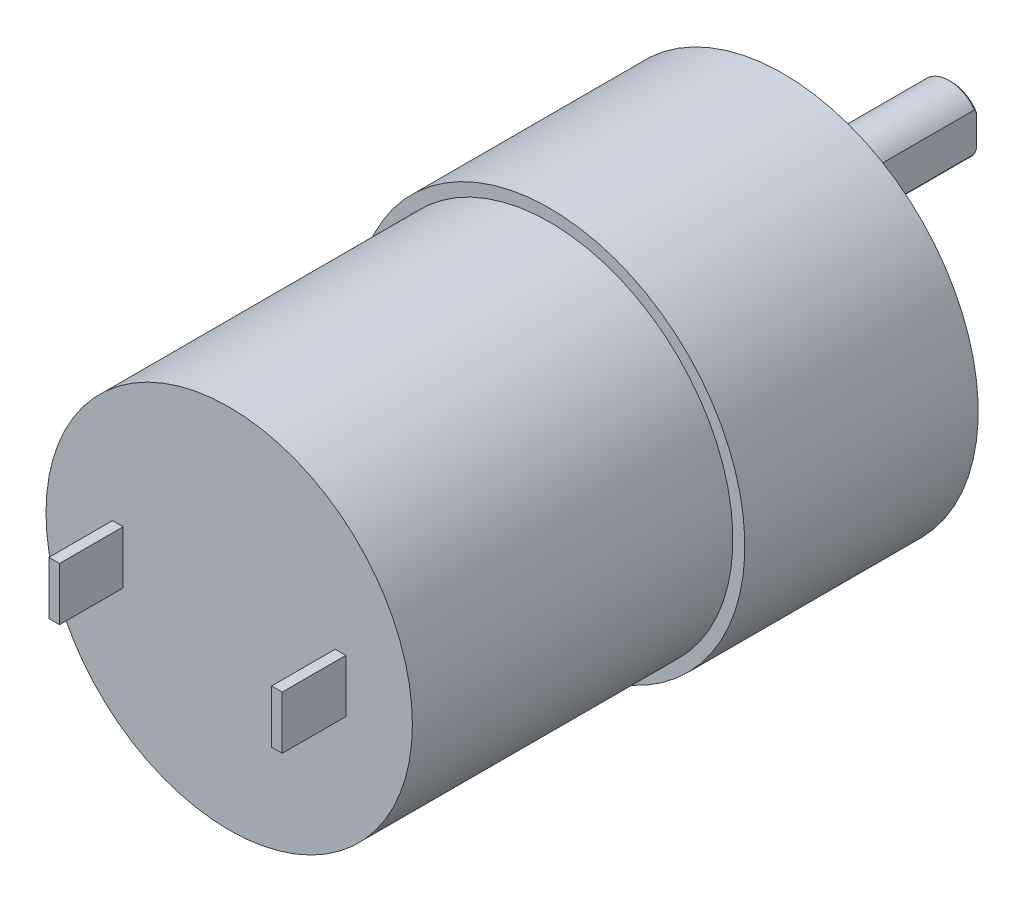
SolidWorks part; units mm, degrees
material "Plain Carbon Steel"
ref_plane "Front Plane" through (0, 0, 0) normal (0, 0, 1) x (1, 0, 0)
ref_plane "Top Plane" through (0, 0, 0) normal (0, 1, 0) x (1, 0, 0)
ref_plane "Right Plane" through (0, 0, 0) normal (1, 0, 0) x (0, 0, -1)
sketch "Sketch1" plane through (0, 0, 0) normal (0, 0, 1) x (1, 0, 0)
  line L0 (0, 0) -> (-7, 0)
  line L1 (0, 0) -> (-17.272, 0)
  line L2 (0, 0) -> (0, 17.272)
  line L3 (0, 0) -> (0, -15.5)
  line L4 (-4.6, 1.8) -> (-4.6, -1.8)
  line L5 (0, 0) -> (0, -15.5) construction
  circle A0 centre (0, 0) radius 17.272
  circle A1 centre (-7, 0) radius 3
  circle A2 centre (-7, 0) radius 6
  circle A3 centre (0, -15.5) radius 1.5
  circle A4 centre (-13.4234, -7.75) radius 1.5
  circle A5 centre (-13.4234, 7.75) radius 1.5
  circle A6 centre (0, 15.5) radius 1.5
  circle A7 centre (13.4234, 7.75) radius 1.5
  circle A8 centre (13.4234, -7.75) radius 1.5
  point P28 (0, -0.9391)
  point P31 (0, 0)
  point P35 (0, 0)
  dimension "D1" = 34.544
  dimension "D2" = 7
  dimension "D4" = 6
  dimension "D3" = 12
  dimension "D8" = 6
  dimension "D6" = 15.5
  dimension "D7" = 3
  dimension "D5" = 2.4
  dimension "D9" = 15.5
extrude "Boss-Extrude1" add sketch "Sketch1" along normal blind 52.22 contours A0
extrude "Boss-Extrude2" add sketch "Sketch1<3>" against normal blind 6.5 contours A2 A1 | L4 A1 L1 | L1 A1 L4 | L1 A2 A1 | L1 A1 L4 | L4 A1 L1 region at (-7, -5.8658, 0) region at (-2.5, 0.1342, 0) region at (-4.3578, -0.685, 0) region at (-4.3578, 0.685, 0) region at (-7.1451, -1.3055, 0) region at (-7.1451, 1.3055, 0)
sketch "Sketch1<3>" plane through (0, 0, 0) normal (0, 0, 1) x (1, 0, 0) same geometry as "Sketch1"
extrude "Boss-Extrude3" add sketch "Sketch1<4>" against normal blind 22.86 contours L4 A1 L1 | L1 A1 L4 region at (-7.1451, -1.3055, 0) region at (-7.1451, 1.3055, 0)
sketch "Sketch1<4>" plane through (0, 0, 0) normal (0, 0, 1) x (1, 0, 0) same geometry as "Sketch1"
extrude "Boss-Extrude4" add sketch "Sketch1<5>" against normal blind 10.668 contours L4 A1 | L4 A1 L1 region at (-4.3578, -0.685, 0) region at (-4.3578, 0.685, 0)
sketch "Sketch1<5>" plane through (0, 0, 0) normal (0, 0, 1) x (1, 0, 0) same geometry as "Sketch1"
sketch "Sketch2" plane through (0, 0, 52.22) normal (0, 0, 1) x (1, 0, 0)
  line L0 (0, 17.272) -> (0, -17.272) construction
  line L1 (17.272, 0) -> (-17.272, 0) construction
  line L2 (-11, 2.5) -> (-10, 2.5)
  line L3 (-11, 2.5) -> (-11, -2.5)
  line L4 (-11, -2.5) -> (-10, -2.5)
  line L5 (-10, 2.5) -> (-10, -2.5)
  line L6 (10, 2.5) -> (10, -2.5)
  line L7 (11, -2.5) -> (10, -2.5)
  line L8 (11, 2.5) -> (11, -2.5)
  line L9 (11, 2.5) -> (10, 2.5)
  circle A0 centre (0, 0) radius 17.272 construction
  dimension "D1" = 5
  dimension "D2" = 1
  dimension "D3" = 2.5
  dimension "D4" = 10
extrude "Boss-Extrude5" add sketch "Sketch2" along normal blind 6
sketch "Sketch4" plane through (0, 0, 0) normal (0, 0, -1) x (-1, 0, 0)
  circle A0 centre (0, 0) radius 18.4
  dimension "D1" = 36.8
extrude "Boss-Extrude6" add sketch "Sketch4" against normal blind 22
hole_wizard "Tap Drill for M3 Tap1" positions "Sketch8" profile "Sketch7" hole size "M3" standard "ISO"
sketch "Sketch8" plane through (0, 0, 0) normal (0, 0, -1) x (-1, 0, 0)
  point P0 (-13.4234, -7.75)
  point P3 (0, -15.5)
  point P6 (0, 15.5)
  point P9 (13.4234, 7.75)
  point P12 (13.4234, -7.75)
  point P15 (-13.4234, 7.75)
sketch "Sketch7" plane through (13.4234, -7.75, 0) normal (1, 0, 0) x (0, 1, 0)
  line L0 (0, 0) -> (0, 3.7511)
  line L1 (0, 3.7511) -> (1.25, 3)
  line L2 (1.25, 3) -> (1.25, 0)
  line L5 (1.25, 0) -> (0, 0)
  line L10 (0, 3.7511) -> (-1.25, 3) construction
  line L11 (0, -6.35) -> (0, 107.95) construction
  dimension "Hole Dia." = 2.5
  dimension "Hole Depth" = 3
  dimension "Drill Angle" = 118
chamfer "Chamfer1" distance 0.2 angle 45 1 edges at (-10, 0, -22.86)
chamfer "Chamfer2" distance 0.5 angle 45 1 edges at (-1, 0, -6.5)
